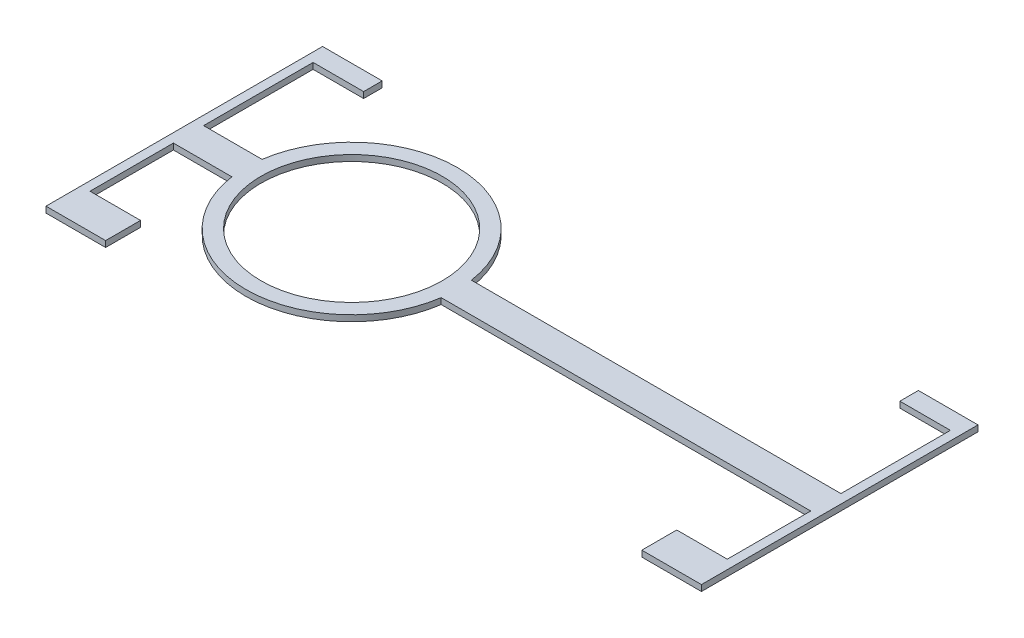
SolidWorks part; units mm, degrees
ref_plane "정면" through (0, 0, 0) normal (0, 0, 1) x (1, 0, 0)
ref_plane "윗면" through (0, 0, 0) normal (0, 1, 0) x (1, 0, 0)
ref_plane "우측면" through (0, 0, 0) normal (1, 0, 0) x (0, 0, -1)
sketch "스케치2" plane through (0, 0, 0) normal (0, 1, 0) x (1, 0, 0)
  line L0 (0, 0) -> (105.5, 0) construction
  line L5 (0, 0) -> (0, 125.6964) construction
  line L6 (-51.5, 0) -> (0, 0) construction
  line L7 (-105.5, 41.2437) -> (-105.5, 5)
  line L8 (105.5, 41.2437) -> (105.5, 5)
  line L9 (-81.5, 0) -> (-105.5, 0) construction
  line L10 (-108.5, 47.3807) -> (-108.5, -44.1848)
  line L11 (108.5, 47.3807) -> (108.5, -44.1848)
  line L12 (-86.141, 5) -> (-105.5, 5)
  line L13 (-16.859, 5) -> (105.5, 5)
  line L14 (-16.859, -5) -> (105.5, -5)
  line L15 (-86.141, -5) -> (-105.5, -5)
  line L16 (-105.5, -5) -> (-105.5, -32.6246)
  line L17 (105.5, -5) -> (105.5, -32.6246)
  line L18 (-105.5, -32.6246) -> (-88.7642, -32.6246)
  line L19 (-88.7642, -32.6246) -> (-88.7642, -44.1848)
  line L20 (-88.7642, -44.1848) -> (-108.5, -44.1848)
  line L21 (-108.5, 47.3807) -> (-88.7642, 47.3807)
  line L22 (-88.7642, 47.3807) -> (-88.7642, 41.2437)
  line L23 (-88.7642, 41.2437) -> (-105.5, 41.2437)
  line L24 (88.7642, -32.6246) -> (88.7642, -44.1848)
  line L25 (105.5, -32.6246) -> (88.7642, -32.6246)
  line L26 (88.7642, -44.1848) -> (108.5, -44.1848)
  line L27 (108.5, 47.3807) -> (88.7642, 47.3807)
  line L28 (88.7642, 47.3807) -> (88.7642, 41.2437)
  line L29 (88.7642, 41.2437) -> (105.5, 41.2437)
  circle A0 centre (-51.5, 0) radius 30
  arc A1 (-86.141, -5) -> (-16.859, -5) centre (-51.5, 0) ccw
  arc A2 (-16.859, 5) -> (-86.141, 5) centre (-51.5, 0) ccw
  dimension "D1" = 60
  dimension "D4" = 70
  dimension "D2" = 211
  dimension "D3" = 24
  dimension "D6" = 3
  dimension "D7" = 10
extrude "보스-돌출1" add sketch "스케치2" along normal blind 2
